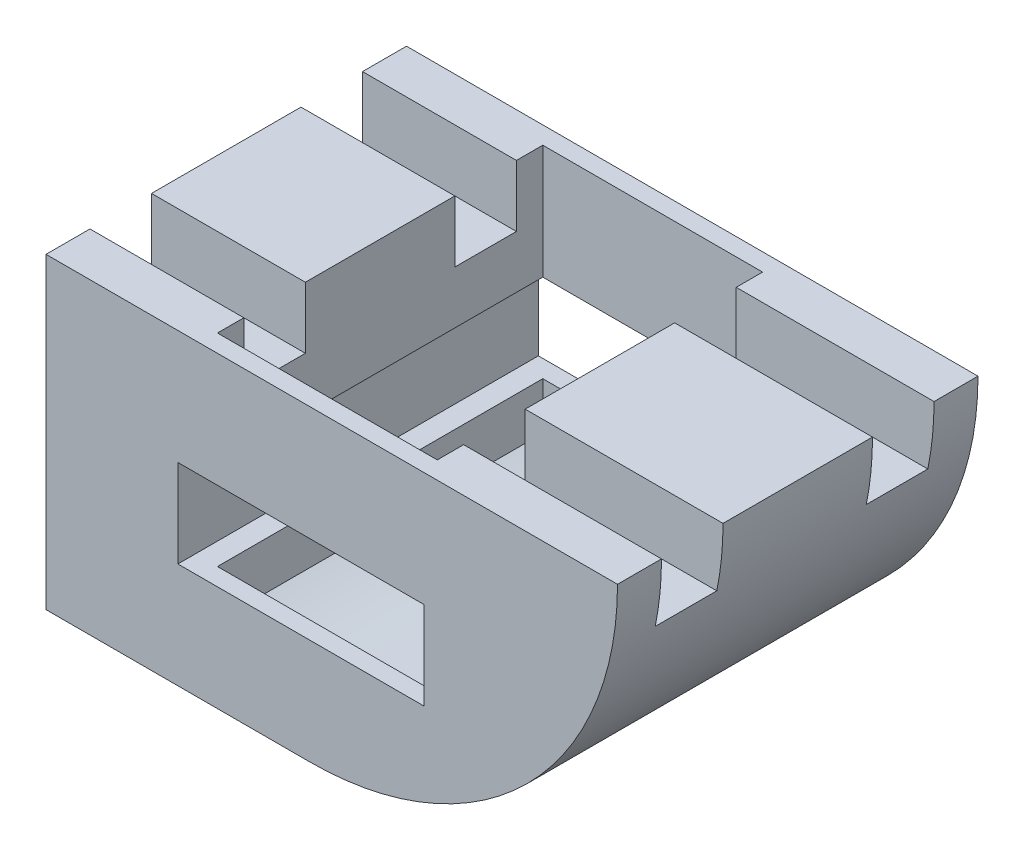
SolidWorks part; units mm, degrees
ref_plane "Front Plane" through (0, 0, 0) normal (0, 0, 1) x (1, 0, 0)
ref_plane "Top Plane" through (0, 0, 0) normal (0, 1, 0) x (1, 0, 0)
ref_plane "Right Plane" through (0, 0, 0) normal (1, 0, 0) x (0, 0, -1)
sketch "Sketch1" plane through (0, 0, 0) normal (0, 0, 1) x (1, 0, 0)
  line L0 (-35, 0) -> (35, 0)
  circle A0 centre (0, 0) radius 35
  dimension "D1" = 70
extrude "Boss-Extrude1" add sketch "Sketch1" along normal blind 45 contours L0 A0 region at (0, -14.8545, 0)
sketch "Sketch2" plane through (0, 0, 0) normal (0, 1, 0) x (1, 0, 0)
  line L0 (-35, 0) -> (35, 0) construction
  line L1 (-31, -4) -> (0.5147, -4)
  line L2 (-31, -4) -> (-31, -41)
  line L3 (-31, -41) -> (0, -41)
  line L5 (-35, -45) -> (35, -45) construction
  line L6 (-35, -45) -> (-35, 0) construction
  line L7 (0, 0) -> (0, -45) construction
  line L8 (-31, -4) -> (0.5147, -4)
  line L9 (-31, -4) -> (-31, -41)
  line L10 (-31, -41) -> (0, -41)
  line L13 (-31, -4) -> (0, -4)
  line L14 (-31, -4) -> (-31, -41)
  line L15 (-31, -41) -> (0, -41)
  line L16 (0, -4) -> (0, -41)
  dimension "D1" = 4
  dimension "D2" = 4
  dimension "D3" = 4
ref_axis "Axis1" through (0, 0, 45) along (0, 0, -1)
revolve "Cut-Revolve1" cut sketch "Sketch2" angle 360 about L7 region at (-15.5, 0, 22.5)
sketch "Sketch3" plane through (0, 0, 45) normal (0, 0, 1) x (1, 0, 0)
  line L0 (-17.5, 0) -> (-17.5, -35)
  line L1 (0, 0) -> (-35, 0)
  line L4 (0, 0) -> (0, -35)
  line L9 (-35, -35) -> (-17.5, -35)
  line L10 (-35, 0) -> (-35, -35)
  line L11 (-35, 0) -> (-17.5, 0)
  line L12 (-35, -35) -> (0, -35)
  line L13 (-35, 0) -> (-35, -35)
  arc A0 (-35, 0) -> (35, 0) centre (0, 0) ccw construction
  line M1 (35, 0) -> (-35, 0)
  arc M2 (-35, 0) -> (35, 0) centre (0, 0) ccw
extrude "Boss-Extrude3" add sketch "Sketch3" against normal blind 45 contours L10 L9 L0 M2 | L0 L12 M2 | L0 M1 M2 region at (-24.6757, -11.8721, 45) region at (-13.1858, -33.611, 45) region at (-28.7561, -26.4591, 45)
sketch "Sketch4" plane through (-35, 0, 0) normal (-1, 0, 0) x (0, 0, 1)
  line L0 (0, -35) -> (45, -35) construction
  line L2 (0, 0) -> (0, -35) construction
  line L3 (0, 0) -> (45, 0) construction
  line L4 (45, 0) -> (22.5, 0) construction
  line L5 (22.5, 0) -> (22.5, -35) construction
  circle A0 centre (10, -17.5) radius 5.05
  circle A1 centre (35, -17.5) radius 5.05
  dimension "D1" = 10.1
  dimension "D2" = 17.5
  dimension "D3" = 10
extrude "Cut-Extrude1" cut sketch "Sketch4" against normal blind 12
sketch "Sketch5" plane through (0, 0, 0) normal (0, 0, -1) x (-1, 0, 0)
  line L0 (35, -35) -> (0, -35) construction
  line L1 (35, 0) -> (30, 0)
  line L2 (35, 0) -> (35, -35)
  line L3 (35, -35) -> (30, -35)
  line L4 (30, 0) -> (30, -35)
  dimension "D1" = 5
extrude "Cut-Extrude2" cut sketch "Sketch5" against normal through all
sketch "Sketch6" plane through (0, 0, 41) normal (0, 0, -1) x (-1, 0, 0)
  line L0 (0, -31) -> (0, 0)
  line L1 (0, 0) -> (-31, 0)
  line L2 (0, 0) -> (-12.5, 0)
  line L3 (-12.5, 0) -> (-12.5, -28.3681)
  line L5 (17.5, 0) -> (12.5, 0)
  line L6 (17.5, 0) -> (17.5, -28.3681)
  line L7 (17.5, -28.3681) -> (12.5, -28.3681)
  line L8 (12.5, 0) -> (12.5, -28.3681)
  circle A0 centre (0, 0) radius 31
  line M1 (17.5, -25.5881) -> (17.5, 0)
  line M2 (17.5, 0) -> (-31, 0)
  arc M3 (-31, 0) -> (17.5, -25.5881) centre (0, 0) ccw
  dimension "D1" = 12.5
  dimension "D2" = 5
extrude "Boss-Extrude5" add sketch "Sketch6" along normal blind 37 contours L3 L1 M3 | L8 M2 M3 M1 region at (20.1294, -11.2411, 41) region at (-14.9573, -13.5514, 41)
sketch "Sketch7" plane through (0, 0, 0) normal (0, 0, -1) x (-1, 0, 0)
  line L5 (-35, 0) -> (-12.5, 0)
  line L6 (-35, 0) -> (-35, -7.441)
  line L7 (-35, -7.441) -> (-12.5, -7.441)
  line L8 (-12.5, 0) -> (-12.5, -7.441)
  line L9 (0, 0) -> (0, 11.2128) construction
  line L10 (35, 0) -> (35, -7.441)
  line L11 (35, 0) -> (12.5, 0)
  line L12 (35, -7.441) -> (12.5, -7.441)
  line L13 (12.5, 0) -> (12.5, -7.441)
  circle A0 centre (0, 0) radius 35
  line M6 (30, -35) -> (30, 0)
  line M7 (30, 0) -> (-35, 0)
  arc M8 (-35, 0) -> (0, -35) centre (0, 0) ccw
  dimension "D1" = 22.5
extrude "Boss-Extrude6" add sketch "Sketch7" along normal blind 5 contours L8 L7 M7 M8 | L13 L12 M7 M6 region at (23.6185, -3.6982, 0) region at (-21.25, -3.7205, 0)
ref_plane "Plane1" through (0, 0, 22.5) normal (0, 0, -1) x (-1, 0, 0)
mirror "Mirror1" about plane through (0, 0, 22.5) normal (0, 0, -1) of "Boss-Extrude6"
sketch "Sketch9" plane through (0, 0, 0) normal (0, 1, 0) x (1, 0, 0)
  line L0 (12.5, -50) -> (35, -50) construction
  line L5 (35, 5) -> (20, 5)
  line L6 (35, 5) -> (35, -50)
  line L7 (35, -50) -> (20, -50)
  line L8 (20, 5) -> (20, -50)
  line L9 (-30, -50) -> (-12.5, -50) construction
  line L10 (-30, 5) -> (-20, 5)
  line L11 (-30, 5) -> (-30, -50)
  line L12 (-30, -50) -> (-20, -50)
  line L13 (-20, 5) -> (-20, -50)
  dimension "D1" = 10
  dimension "D2" = 15
extrude "Boss-Extrude7" add sketch "Sketch9" along normal blind 3
sketch "Sketch12" plane through (0, 3, 0) normal (0, 1, 0) x (1, 0, 0)
  line L0 (35, -50) -> (35, 5) construction
  line L1 (35, 5) -> (20, 5) construction
  line L3 (19.25, -22.5) -> (-19.25, -22.5) construction
  line L4 (35, -22.5) -> (0, -22.5) construction
  line L6 (-30, 5) -> (-30, -50) construction
  line L7 (0, -22.5) -> (0, -55.2431) construction
  circle A0 centre (26, 1.5) radius 1.55
  circle A1 centre (26, -10.5) radius 1.55
  circle A2 centre (26, -34.5) radius 1.55
  circle A3 centre (26, -46.5) radius 1.55
  circle A7 centre (-26, 1.5) radius 1.55
  circle A8 centre (-26, -10.5) radius 1.55
  circle A9 centre (-26, -34.5) radius 1.55
  circle A10 centre (-26, -46.5) radius 1.55
  dimension "D1" = 3.1
  dimension "D2" = 9
  dimension "D3" = 3.5
  dimension "D4" = 12
  dimension "D5" = 9
  dimension "D6" = 3.1
  dimension "D7" = 4
  dimension "D8" = 2
extrude "Cut-Extrude5" cut sketch "Sketch12" against normal blind 5
sketch "Sketch13" plane through (35, 0, 0) normal (1, 0, 0) x (0, 0, -1)
  line L1 (-50, 3) -> (-43, 3)
  line L2 (-50, 3) -> (-50, -7)
  line L3 (-50, -7) -> (-43, -7)
  line L4 (-43, 3) -> (-43, -7)
  line L6 (-44.95, -2) -> (-44.95, 3) construction
  line L7 (-44.95, -2) -> (-48.05, -2) construction
  line L8 (-50, 3) -> (5, 3) construction
  line L9 (-38, 3) -> (-31, 3)
  line L10 (-38, 3) -> (-38, -7)
  line L11 (-38, -7) -> (-31, -7)
  line L12 (-31, 3) -> (-31, -7)
  line L13 (-36.05, 3) -> (-36.05, -2) construction
  line L14 (-32.95, -2) -> (-32.95, 3) construction
  line L15 (-32.95, -2) -> (-36.05, -2) construction
  line L16 (-22.5, 3) -> (-22.5, 8.3556) construction
  line L17 (-22.5, -19.25) -> (-22.5, 19.25) construction
  line L18 (-14, 3) -> (-14, -7)
  line L19 (-7, -7) -> (-14, -7)
  line L20 (-7, 3) -> (-7, -7)
  line L21 (-7, 3) -> (-14, 3)
  line L22 (-2, 3) -> (-2, -7)
  line L23 (5, -7) -> (-2, -7)
  line L24 (5, 3) -> (5, -7)
  line L25 (5, 3) -> (-2, 3)
  line L27 (-50, 3) -> (5, 3)
  line L28 (-50, 3) -> (-50, 0)
  line L29 (-50, 0) -> (5, 0)
  line L30 (5, 3) -> (5, 0)
  line M9 (-50, 0) -> (5, 0)
  dimension "D1" = 1.95
  dimension "D2" = 5
  dimension "D3" = 1.95
  dimension "D4" = 1.95
  dimension "D5" = 5
extrude "Cut-Extrude6" cut sketch "Sketch13" against normal through all contours L4 L2 L3 M9 | L12 L10 L11 M9 | L20 L18 L19 M9 | L24 L22 L23 M9 region at (35, -3.5, 46.5) region at (35, -3.5, 34.5) region at (35, -3.5, 10.5) region at (35, -3.5, -1.5)
sketch "Sketch14" plane through (0, 0, 50) normal (0, 0, 1) x (1, 0, 0)
  line L1 (-30, 3) -> (35, 3)
  line L2 (-30, 3) -> (-30, 0)
  line L3 (-30, 0) -> (35, 0)
  line L4 (35, 3) -> (35, 0)
extrude "Cut-Extrude7" cut sketch "Sketch14" against normal through all
sketch "Sketch15" plane through (-30, 0, 0) normal (-1, 0, 0) x (0, 0, 1)
  line L0 (45, -35) -> (0, -35) construction
  line L1 (-5, -7) -> (0, -7)
  line L2 (-5, -7) -> (-5, -7.441)
  line L3 (-5, -7.441) -> (0, -7.441)
  line L4 (0, -7) -> (0, -7.441)
  line L5 (45, -7.441) -> (50, -7.441)
  line L6 (45, -7.441) -> (45, -7)
  line L7 (45, -7) -> (50, -7)
  line L8 (50, -7.441) -> (50, -7)
  line L9 (2, -7) -> (0, -7)
  line L10 (2, -7) -> (2, -35)
  line L11 (2, -35) -> (0, -35)
  line L12 (0, -7) -> (0, -35)
  line L13 (45, -7) -> (43, -7)
  line L14 (45, -7) -> (45, -35)
  line L15 (45, -35) -> (43, -35)
  line L16 (43, -7) -> (43, -35)
  line M14 (2, -7) -> (-5, -7)
  line M15 (-5, -7) -> (-5, -7.441)
  line M16 (-5, -7.441) -> (0, -7.441)
  line M17 (0, -7.441) -> (0, -35)
  line M18 (0, -35) -> (45, -35)
  line M19 (45, -35) -> (45, -7.441)
  line M20 (45, -7.441) -> (50, -7.441)
  line M21 (50, -7.441) -> (50, -7)
  line M22 (50, -7) -> (43, -7)
extrude "Cut-Extrude8" cut sketch "Sketch15" against normal through all contours L4 M14 M15 M16 | L10 L4 M14 M17 M18 | L6 M20 M21 M22 | L16 L6 M22 M18 M19 region at (-30, -21, 44) region at (-30, -7.2205, -2.5) region at (-30, -21, 1) region at (-30, -7.2205, 47.5)
sketch "Sketch16" plane through (-30, 0, 0) normal (-1, 0, 0) x (0, 0, 1)
  line L0 (22.5, 55) -> (22.5, -55) construction
  circle A0 centre (29.5, -18.5) radius 5
  circle A1 centre (35, -17.5) radius 5.05 construction
  circle A2 centre (35, -17.5) radius 5.05
  circle A3 centre (15.5, -18.5) radius 5
  circle M1 centre (10, -17.5) radius 5.05
  circle M2 centre (35, -17.5) radius 5.05
  dimension "D1" = 5.5
  dimension "D2" = 1
extrude "Cut-Extrude9" cut sketch "Sketch16" against normal blind 5 contours A3 M1 | A0 M2 region at (-30, -18.7477, 28.1374) region at (-30, -18.7477, 16.8626)
sketch "Sketch17" plane through (0, 0, 43) normal (0, 0, 1) x (1, 0, 0)
  line L0 (-30, 0) -> (-30, -35) construction
  line L1 (-15, -13) -> (13, -13)
  line L2 (-15, -13) -> (-15, -23)
  line L3 (-15, -23) -> (13, -23)
  line L4 (13, -13) -> (13, -23)
  line L5 (0, -35) -> (-30, -35) construction
  dimension "D1" = 15
  dimension "D2" = 28
  dimension "D3" = 12
  dimension "D4" = 10
extrude "Cut-Extrude10" cut sketch "Sketch17" against normal through all
